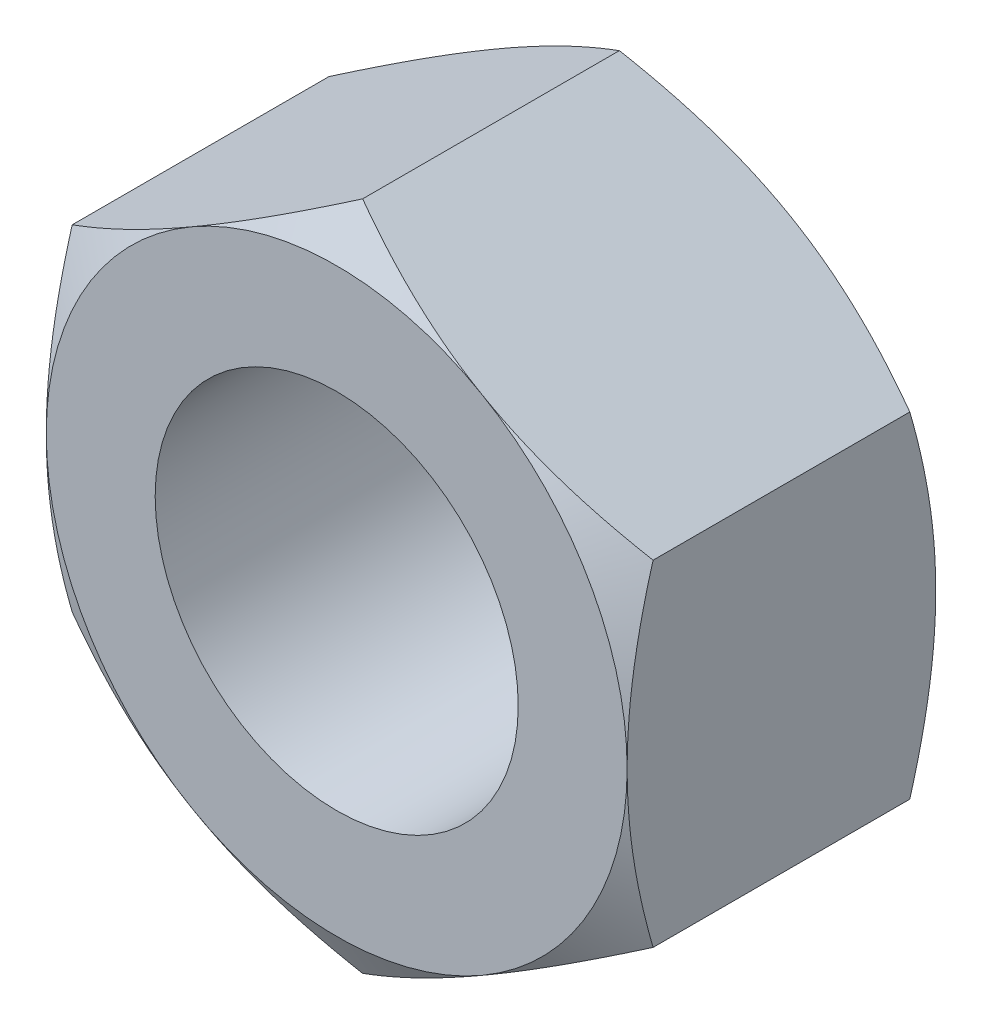
SolidWorks part; units mm, degrees
ref_plane "Front" through (0, 0, 0) normal (0, 0, 1) x (1, 0, 0)
ref_plane "Top" through (0, 0, 0) normal (0, 1, 0) x (1, 0, 0)
ref_plane "Right" through (0, 0, 0) normal (1, 0, 0) x (0, 0, -1)
sketch "Sketch1" plane through (0, 0, 0) normal (0, 0, 1) x (1, 0, 0)
  line L1 (-6.35, 3.6662) -> (-6.35, -3.6662)
  line L2 (-6.35, -3.6662) -> (0, -7.3323)
  line L3 (0, -7.3323) -> (6.35, -3.6662)
  line L4 (6.35, -3.6662) -> (6.35, 3.6662)
  line L5 (6.35, 3.6662) -> (0, 7.3323)
  line L6 (0, 7.3323) -> (-6.35, 3.6662)
  circle A0 centre (0, 0) radius 6.35 construction
  circle A1 centre (0, 0) radius 3.9688
  point P10 (0, 3.9688)
  dimension "hex" = 12.7
  dimension "dia" = 7.9375
extrude "Extrude1" add sketch "Sketch1" along normal mid plane 6.7469
sketch "Sketch4" plane through (0, 0, -3.3734) normal (0, 0, -1) x (-1, 0, 0)
  circle A0 centre (0, 0) radius 3.9688 construction
  circle A1 centre (0, 0) radius 3.9688
curve "Helix/Spiral3" pitch 1.4111 height 8.0962 turns 5.7375
sketch "Sketch3" plane through (0, 0, 0) normal (1, 0, 0) x (0, 0, -1)
  line L0 (3.3734, 3.9688) -> (4.6082, 3.9688)
  line L1 (4.6082, 3.9688) -> (4.079, 3.0522)
  line L2 (4.079, 3.0522) -> (3.9026, 3.0522)
  line L3 (3.9026, 3.0522) -> (3.3734, 3.9688)
  line L4 (3.638, 3.5105) -> (4.3436, 3.5105) construction
  dimension "D1" = 60
  dimension "D2" = 0.7056
  dimension "D3" = 0.1764
sweep "Sweep1" [suppressed] add profiles "Sketch3" path "Helix/Spiral3"
sketch "Sketch6" [suppressed] plane through (0, 0, 0) normal (1, 0, 0) x (0, 0, -1)
  line L0 (-3.7262, 4.3215) -> (-3.0207, 3.616)
  line L1 (-3.0207, 3.616) -> (-3.0207, 0) construction
  line L2 (4.7445, 0) -> (-4.7445, 0) construction
  line L3 (-3.0207, 0) -> (-4.7235, 0)
  line L4 (-4.7235, 0) -> (-4.7235, 4.3215)
  line L5 (-4.7235, 4.3215) -> (-3.7262, 4.3215)
  line L6 (-3.0207, 3.616) -> (0.5953, 0)
  line L7 (0.5953, 0) -> (-3.0207, 0)
  line L8 (-3.3734, -3.6662) -> (-3.3734, 3.6662) construction
  point P2 (-3.3734, 3.9688)
  dimension "D2" = 0.7056
  dimension "D1" = 45
revolve "Cut-Revolve1" [suppressed] cut sketch "Sketch6" angle 360 about L3
sketch "Sketch7" plane through (0, 0, 3.3734) normal (0, 0, 1) x (1, 0, 0)
  circle A0 centre (0, 0) radius 6.35 construction
  circle A1 centre (0, 0) radius 6.35
extrude "Extrude2" cut sketch "Sketch7" against normal blind 25.4 draft 60 flip side to cut
mirror "Mirror1" about plane through (0, 0, 0) normal (0, 0, 1) of "Extrude2", "Cut-Revolve1"
sketch "Sketch8" [suppressed] plane through (0, 0, 3.3734) normal (0, 0, 1) x (1, 0, 0)
  line L0 (-2.8063, 2.8063) -> (0, 0) construction
  line L1 (0, -4.7445) -> (0, 4.7445) construction
  circle A0 centre (0, 0) radius 3.9688 construction
  point P0 (-2.8063, 2.8063)
  dimension "D1" = 45
ref_axis "Axis1" through (0, 0, 3.7108) along (0, 0, -1)
equation "\"D3@Helix/Spiral3\" = \"length@Extrude1\" * 1.2"
equation "\"D2@Sketch3\" = \"D4@Helix/Spiral3\" * .5"
equation "\"D3@Sketch3\" = \"D4@Helix/Spiral3\" * .125"
equation "\"D2@Sketch6\" = \"D4@Helix/Spiral3\" * .5"
